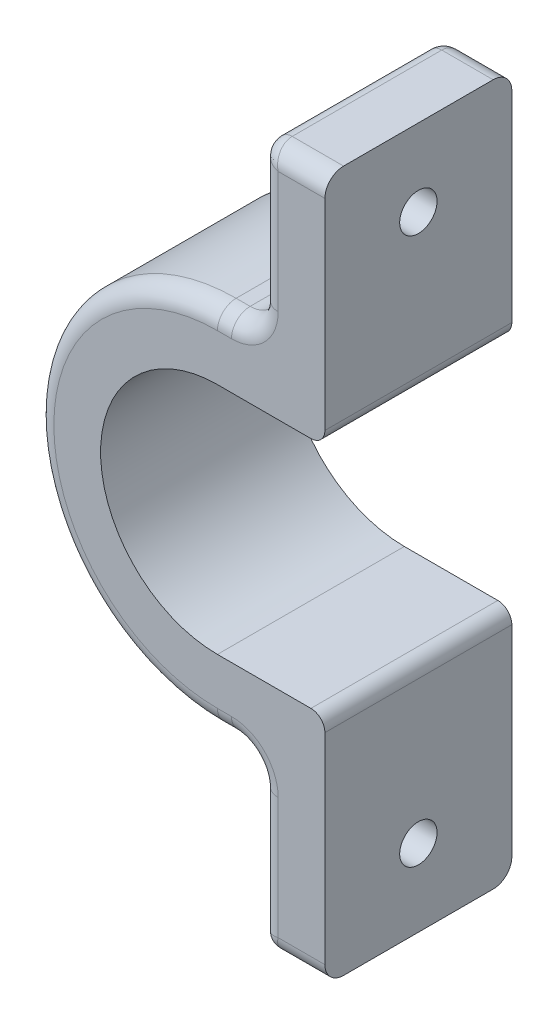
SolidWorks part; units mm, degrees
ref_plane "Front Plane" through (0, 0, 0) normal (0, 0, 1) x (1, 0, 0)
ref_plane "Top Plane" through (0, 0, 0) normal (0, 1, 0) x (1, 0, 0)
ref_plane "Right Plane" through (0, 0, 0) normal (1, 0, 0) x (0, 0, -1)
sketch "Sketch1" plane through (0, 0, 0) normal (0, 0, 1) x (1, 0, 0)
  line L0 (9.1417, 17.9891) -> (19.1417, 17.9891)
  line L1 (9.1417, -7.0109) -> (19.1417, -7.0109)
  line L2 (20.6417, -8.5109) -> (20.6417, -11.9624)
  line L3 (10.6417, -14.0109) -> (9.1417, -14.0109)
  line L5 (9.1417, 24.9891) -> (10.6417, 24.9891)
  line L6 (20.6417, 26.3318) -> (20.6417, 19.4891)
  line L7 (20.6417, 26.3318) -> (20.6417, 42.9891)
  line L8 (20.6417, 42.9891) -> (15.1417, 42.9891)
  line L9 (13.6417, 41.4891) -> (13.6417, 27.9891)
  line L10 (20.6417, -11.9624) -> (20.6417, -32.0109)
  line L11 (20.6417, -32.0109) -> (15.1417, -32.0109)
  line L12 (13.6417, -30.5109) -> (13.6417, -17.0109)
  arc A0 (9.1417, 17.9891) -> (9.1417, -7.0109) centre (9.1417, 5.4891) ccw
  arc A1 (9.1417, -14.0109) -> (9.1417, 24.9891) centre (9.1417, 5.4891) cw
  arc A2 (13.6417, -17.0109) -> (10.6417, -14.0109) centre (10.6417, -17.0109) ccw
  arc A3 (13.6417, 27.9891) -> (10.6417, 24.9891) centre (10.6417, 27.9891) cw
  arc A4 (19.1417, -7.0109) -> (20.6417, -8.5109) centre (19.1417, -8.5109) cw
  arc A5 (19.1417, 17.9891) -> (20.6417, 19.4891) centre (19.1417, 19.4891) ccw
  arc A6 (15.1417, 42.9891) -> (13.6417, 41.4891) centre (15.1417, 41.4891) ccw
  arc A7 (15.1417, -32.0109) -> (13.6417, -30.5109) centre (15.1417, -30.5109) cw
  point P25 (20.6417, -7.0109)
  point P28 (20.6417, 17.9891)
  point P31 (9.1417, 5.4891)
  dimension "D5" = 12.5
  dimension "D6" = 7
  dimension "D7" = 3
  dimension "D8" = 1.5
  dimension "D9" = 1.5
  dimension "D1" = 25
  dimension "D2" = 25
  dimension "D3" = 7
  dimension "D4" = 7
  dimension "D10" = 10
  dimension "D11" = 10
extrude "Boss-Extrude1" add sketch "Sketch1" along normal blind 20
sketch "Sketch2" plane through (13.6417, 0, 0) normal (-1, 0, 0) x (0, 0, 1)
  line L3 (0, -23.7609) -> (20, -23.7609) construction
  line L4 (0, -17.0109) -> (0, -30.5109) construction
  line L5 (20, -17.0109) -> (20, -30.5109) construction
  line L6 (0, 34.7391) -> (20, 34.7391) construction
  line L9 (0, 41.4891) -> (0, 27.9891) construction
  line L10 (20, 41.4891) -> (20, 27.9891) construction
  line L11 (10, 41.4891) -> (10, 27.9891) construction
  line L12 (20, 41.4891) -> (0, 41.4891) construction
  line L13 (20, 27.9891) -> (0, 27.9891) construction
  line L14 (20, -17.0109) -> (0, -17.0109) construction
  line L15 (10, -17.0109) -> (10, -30.5109) construction
  line L16 (20, -30.5109) -> (0, -30.5109) construction
  circle A2 centre (10, 34.7391) radius 2
  circle A4 centre (10, -23.7609) radius 2
  dimension "D2" = 4
  dimension "D3" = 4
extrude "Cut-Extrude1" cut sketch "Sketch2" against normal up to surface (7 mm away) up to face at (20.6417, -20.2609, 10)
fillet "Fillet1" radius 2 22 edges at (12.763, 25.8678, 20) (12.763, -14.8895, 20) (12.763, 25.8678, 0) (12.763, -14.8895, 0) (17.8917, 42.9891, 20) (14.081, 42.5498, 20) (13.6417, 34.7391, 20) (9.8917, 24.9891, 20) (17.8917, -32.0109, 20) (14.081, -31.5715, 20) (13.6417, -23.7609, 20) (9.8917, -14.0109, 20) (17.8917, 42.9891, 0) (14.081, 42.5498, 0) (13.6417, 34.7391, 0) (9.8917, 24.9891, 0) (17.8917, -32.0109, 0) (14.081, -31.5715, 0) (13.6417, -23.7609, 0) (9.8917, -14.0109, 0) (-10.3583, 5.4891, 20) (-10.3583, 5.4891, 0)
